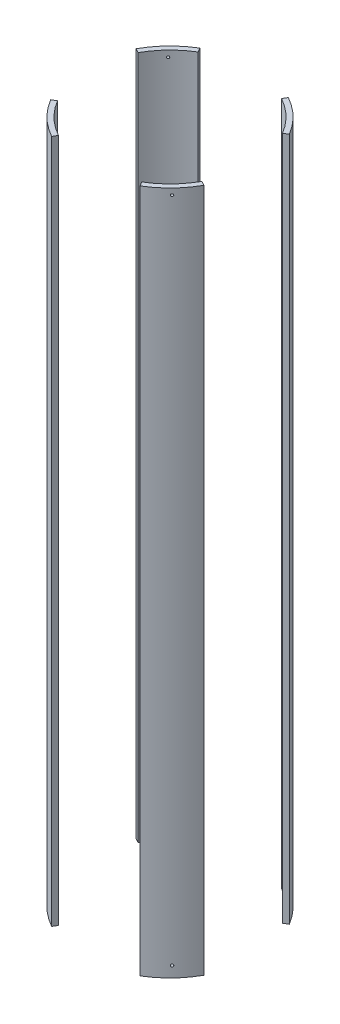
SolidWorks part; units mm, degrees
material "6061-T6 (SS)"
ref_plane "Front Plane" through (0, 0, 0) normal (0, 0, 1) x (1, 0, 0)
ref_plane "Top Plane" through (0, 0, 0) normal (0, 1, 0) x (1, 0, 0)
ref_plane "Right Plane" through (0, 0, 0) normal (1, 0, 0) x (0, 0, -1)
sketch "Sketch2" plane through (0, 0, 0) normal (0, 1, 0) x (1, 0, 0)
  circle A0 centre (0, 0) radius 88.9
  circle A1 centre (0, 0) radius 83.82
  dimension "D1" = 177.8
  dimension "D2" = 167.64
extrude "Boss-Extrude1" add sketch "Sketch2" along normal mid plane 699.0204
sketch "Sketch3" plane through (0, 0, 0) normal (0, 1, 0) x (1, 0, 0)
  line L0 (0, 0) -> (169.6618, 101.6776)
  line L1 (-58.1167, 96.9749) -> (0, 0)
  line L2 (0, 0) -> (53.9, 96.9749)
  line L3 (53.9, 96.9749) -> (-58.1167, 96.9749)
  line L4 (0, 0) -> (70.9917, -118.4586)
  line L5 (70.9917, -118.4586) -> (-65.8409, -118.4586)
  line L6 (-65.8409, -118.4586) -> (0, 0)
  line L7 (169.6618, 101.6776) -> (169.6618, -94.3004)
  line L8 (169.6618, -94.3004) -> (0, 0)
  line L9 (0, 0) -> (-123.7413, 68.7771)
  line L10 (-123.7413, 68.7771) -> (-123.7413, -74.1577)
  line L11 (-123.7413, -74.1577) -> (0, 0)
  dimension "D1" = 60
  dimension "D2" = 60
  dimension "D3" = 60
  dimension "D4" = 60
  dimension "D5" = 30
  dimension "D6" = 30
extrude "Cut-Extrude1" cut sketch "Sketch3" against normal through all both and the other way through all contours L8 L7 L0 | L2 L3 L1 | L10 L11 L9 | L6 L5 L4 region at (-1.4056, 0, -64.65) region at (1.7169, 0, 78.9724) region at (113.1078, 0, -2.4591) region at (-82.4942, 0, 1.7935)
ref_plane "Bolt reference plane" through (-56.3092, 0, 58.1758) normal (0.6955, 0, -0.7185) x (-0.7185, 0, -0.6955)
sketch "Sketch5" plane through (-56.3092, 0, 58.1758) normal (0.6955, 0, -0.7185) x (-0.7185, 0, -0.6955)
  line L0 (-23.009, -349.5102) -> (23.009, -349.5102) construction
  circle A0 centre (-0.0228, 343.1602) radius 1.27
  circle A1 centre (-0.0228, -338.3977) radius 1.27
  dimension "D1" = 2.54
  dimension "D4" = 11.1125
  dimension "D2" = 21.717
  dimension "D3" = 6.35
extrude "Bolt holes" cut sketch "Sketch5" against normal through all
pattern_circular "Bolt pattern" count 4 over 360 about axis through (0, 349.5102, 0) along (0, 1, 0) of "Bolt holes"
equation "\"D1@Boss-Extrude1\"=3*12"
